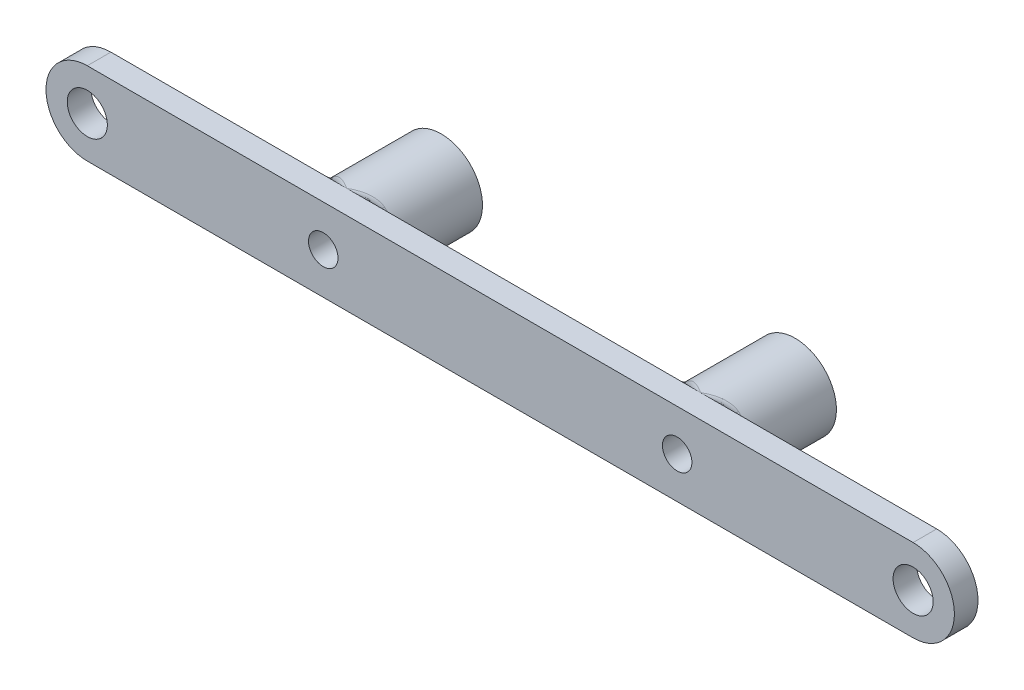
SolidWorks part; units mm, degrees
ref_plane "Спереди" through (0, 0, 0) normal (0, 0, 1) x (1, 0, 0)
ref_plane "Сверху" through (0, 0, 0) normal (0, 1, 0) x (1, 0, 0)
ref_plane "Справа" through (0, 0, 0) normal (1, 0, 0) x (0, 0, -1)
sketch "Эскиз1" plane through (0, 0, 0) normal (0, 0, 1) x (1, 0, 0)
  line L10 (-35, 3.5) -> (35, 3.5)
  line L11 (-35, 0) -> (35, 0) construction
  line L17 (-35, -3.5) -> (35, -3.5)
  arc A8 (35, -3.5) -> (35, 3.5) centre (35, 0) ccw
  arc A11 (-35, 3.5) -> (-35, -3.5) centre (-35, 0) ccw
  circle A12 centre (-35, 0) radius 1.7
  circle A13 centre (35, 0) radius 1.7
  point P2 (0, 0)
  dimension "D6" = 7
  dimension "D1" = 3.4
  dimension "D4" = 70
extrude "Основа" add sketch "Эскиз1" against normal blind 2
sketch "Эскиз2" plane through (0, 0, -2) normal (0, 0, -1) x (-1, 0, 0)
  line L0 (-15, 0) -> (15, 0) construction
  circle A0 centre (-15, 0) radius 3.5
  circle A2 centre (15, 0) radius 3.5
  arc A4 (-35, 3.5) -> (-35, -3.5) centre (-35, 0) ccw construction
  point P3 (0, 0)
  dimension "D1" = 30
extrude "Стойки" add sketch "Эскиз2" along normal blind 8
sketch "Эскиз3" plane through (0, 0, -10) normal (0, 0, -1) x (-1, 0, 0)
  circle A0 centre (-15, 0) radius 1.25
  circle A1 centre (15, 0) radius 1.25
  arc A2 (-15, -3.5) -> (-15, 3.5) centre (-15, 0) ccw construction
  circle A4 centre (15, 0) radius 3.5 construction
  dimension "D1" = 2.5
extrude "Под шурупы для крепления платы" cut sketch "Эскиз3" against normal through all
fillet "Скругление1" radius 1 4 edges at (11.5, 0, -2) (18.5, 0, -2) (-18.5, 0, -2) (-11.5, 0, -2)
